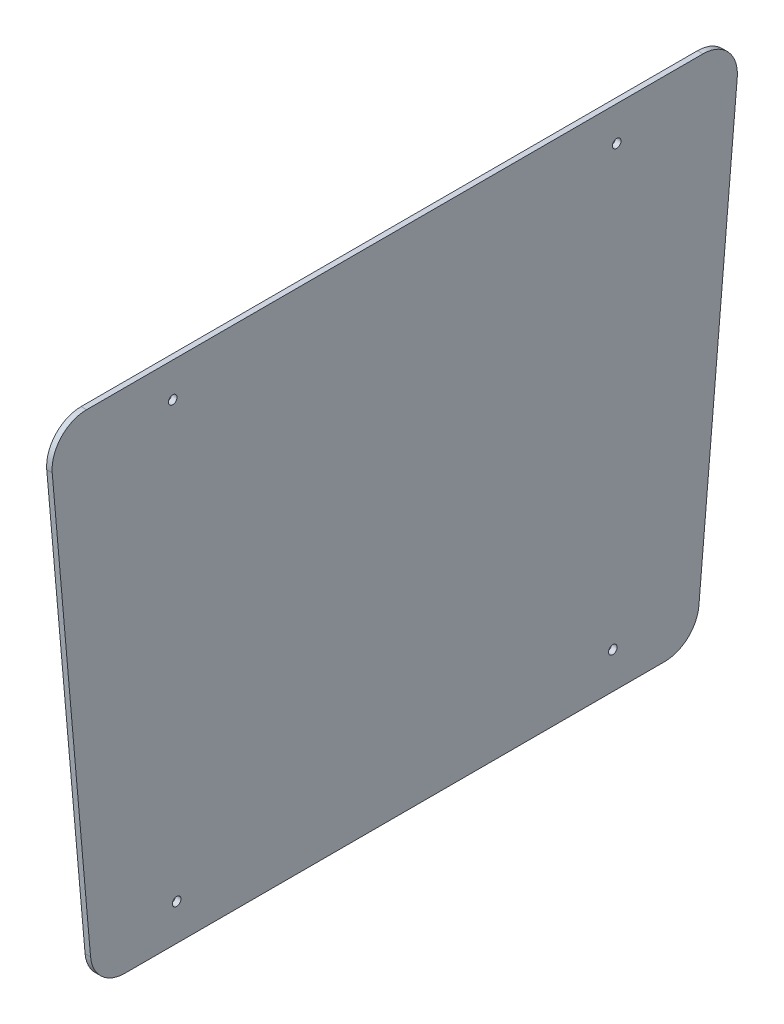
SolidWorks part; units mm, degrees
ref_plane "Front Plane" through (0, 0, 0) normal (0, 0, 1) x (1, 0, 0)
ref_plane "Top Plane" through (0, 0, 0) normal (0, 1, 0) x (1, 0, 0)
ref_plane "Right Plane" through (0, 0, 0) normal (1, 0, 0) x (0, 0, -1)
sketch "Sketch1" plane through (0, 0, 0) normal (1, 0, 0) x (0, 0, -1)
  line L0 (0, 0) -> (-25.7672, 294.52)
  line L1 (-25.7672, 294.52) -> (375.7928, 294.52)
  line L2 (375.7928, 294.52) -> (350.0257, 0)
  line L3 (350.0257, 0) -> (0, 0)
  dimension "D1" = 294.52
  dimension "D2" = 95
  dimension "D3" = 95
  dimension "D4" = 401.56
base flange "Base-Flange1" sketch "Sketch1" thickness 3.175 reverse thickness direction no parameters "D1"=0.7366
fillet "Fillet1" radius 20 4 edges at (-1.5875, 294.52, -375.7928) (-1.5875, 0, -350.0257) (-1.5875, 0, 0) (-1.5875, 294.52, 25.7672)
sketch "Sketch2" plane through (0, 0, 0) normal (1, 0, 0) x (0, 0, -1)
  line L0 (353.9667, 294.52) -> (-3.941, 294.52) construction
  circle A0 centre (46.1134, 274.52) radius 2.5
  circle A1 centre (303.8906, 274.52) radius 2.5
  circle A2 centre (48.4027, 21.1188) radius 2.5
  circle A3 centre (301.6229, 21.1188) radius 2.5
  point P10 (0, 0)
  point P13 (0, 0)
  point P14 (0, 0)
  point P17 (0, 0)
  point P18 (0, 0)
  dimension "D1" = 5
  dimension "D2" = 5
  dimension "D3" = 5
  dimension "D4" = 5
  dimension "D5" = 20
  dimension "D6" = 20
  dimension "D7" = 70
  dimension "D8" = 70
  dimension "D9" = 50
  dimension "D10" = 50
  dimension "D11" = 253.4012
extrude "Cut-Extrude1" cut sketch "Sketch2" against normal blind 10 normal cut yes
sketch "Bend-Lines1" [suppressed] plane through (0, 0, 0) normal (0, 1, 0) x (1, 0, 0)
sketch "Bounding-Box1" [suppressed] plane through (0, 0, 0) normal (0, 1, 0) x (1, 0, 0)
sheet metal parameters "Sheet-Metal1" thickness 3.175 parameters "D1"=0.7366
flat pattern "Flat-Pattern1" [suppressed]
sketch "Bend-Lines2" plane through (0, 0, 0) normal (0, 1, 0) x (1, 0, 0)
sketch3d "Bounding-Box2" [suppressed]
  line L0 (373.9666, 0, 0) -> (-23.941, 0, 0) construction
  line L1 (373.9666, 294.52, 0) -> (-23.941, 294.52, 0) construction
  line L2 (373.9666, 0, 0) -> (373.9666, 294.52, 0) construction
  line L3 (-23.941, 0, 0) -> (-23.941, 294.52, 0) construction
sheet metal parameters "Sheet-Metal2" thickness 3.175 parameters "D1"=0.7366
flat pattern "Flat-Pattern1"
sketch "Bend-Lines2" plane through (0, 0, 0) normal (0, 1, 0) x (1, 0, 0)
sketch3d "Bounding-Box2" [suppressed]
  line L0 (373.9666, 0, 0) -> (-23.941, 0, 0) construction
  line L1 (373.9666, 294.52, 0) -> (-23.941, 294.52, 0) construction
  line L2 (373.9666, 0, 0) -> (373.9666, 294.52, 0) construction
  line L3 (-23.941, 0, 0) -> (-23.941, 294.52, 0) construction
